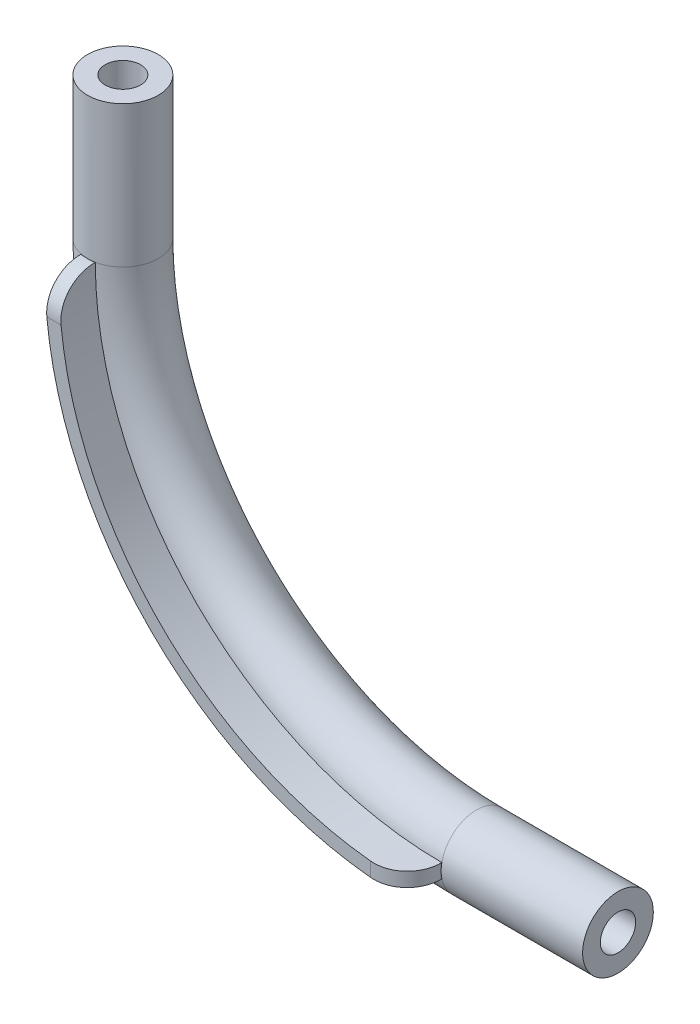
SolidWorks part; units mm, degrees
ref_plane "前基準面" through (0, 0, 0) normal (0, 0, 1) x (1, 0, 0)
ref_plane "上基準面" through (0, 0, 0) normal (0, 1, 0) x (1, 0, 0)
ref_plane "右基準面" through (0, 0, 0) normal (1, 0, 0) x (0, 0, -1)
sketch "草圖4" plane through (0, 0, 0) normal (0, 1, 0) x (1, 0, 0)
  line L0 (0, 3.4749) -> (0, -3.49) construction
  line L1 (0, -55) -> (0, 55) construction
  line L2 (-55, 0) -> (55, 0) construction
  circle A0 centre (-50, 0) radius 5
  dimension "D1" = 50
  dimension "D2" = 10
revolve "旋轉1" add sketch "草圖4" angle 90 about L0
sketch "草圖5" plane through (0, 0, 0) normal (1, 0, 0) x (0, 0, -1)
  circle A0 centre (0, -50) radius 5 construction
  circle A1 centre (0, -50) radius 5
  circle A2 centre (0, -50) radius 2.5
  dimension "D1" = 5
extrude "填料-伸長4" add sketch "草圖5" along normal blind 20 contours A1 | A2
sketch "草圖6" plane through (0, 0, 0) normal (0, 1, 0) x (1, 0, 0)
  circle A0 centre (-50, 0) radius 5 construction
  circle A1 centre (-50, 0) radius 5
  circle A2 centre (-50, 0) radius 2.5
  dimension "D1" = 5
extrude "填料-伸長5" add sketch "草圖6" along normal blind 20
sketch "草圖7" plane through (0, 0, 0) normal (0, 0, 1) x (1, 0, 0)
  line L0 (10.0499, -50) -> (-4.9615, -50) construction
  line L2 (-3.7268, -49) -> (6.7893, -49) construction
  line L3 (-3.7268, -51) -> (6.7893, -51) construction
  line L4 (-49, 0) -> (-51, 0)
  line L5 (0, -49) -> (0, -51)
  arc A0 (-49, 0) -> (0, -49) centre (0, 0) ccw
  arc A1 (-51, 0) -> (0, -51) centre (0, 0) ccw
  dimension "D1" = 1
extrude "填料-伸長6" add sketch "草圖7" along normal blind 10
fillet "圓角1" radius 5 2 edges at (0, -50, 10) (-50, 0, 10)
